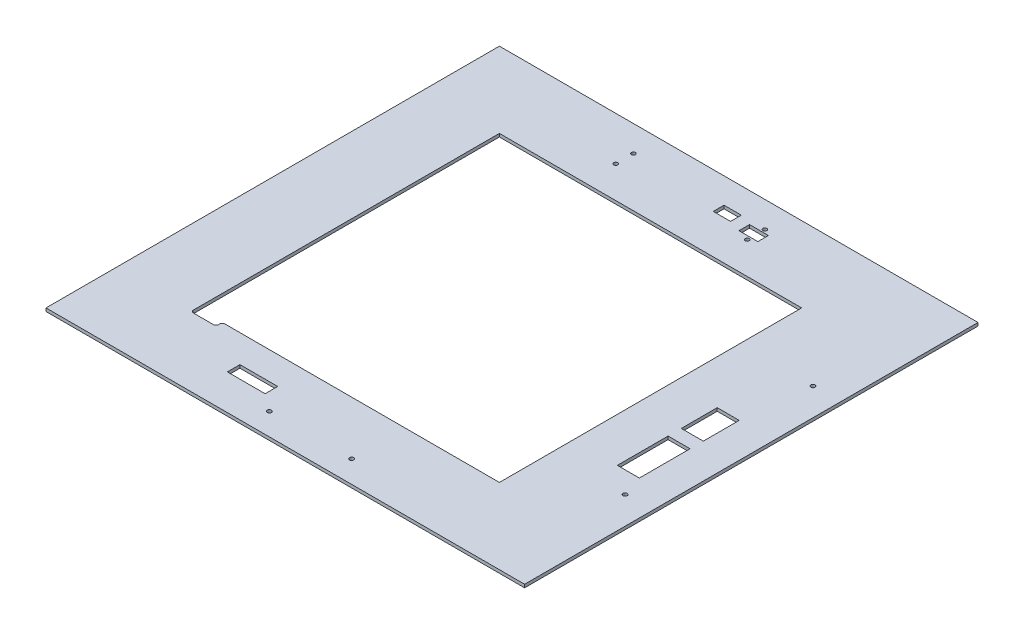
SolidWorks part; units mm, degrees
ref_plane "Front" through (0, 0, 0) normal (0, 0, 1) x (1, 0, 0)
ref_plane "Top" through (0, 0, 0) normal (0, 1, 0) x (1, 0, 0)
ref_plane "Right" through (0, 0, 0) normal (1, 0, 0) x (0, 0, -1)
sketch "Sketch1" plane through (0, 0, 0) normal (0, 1, 0) x (1, 0, 0)
  line L0 (-55, 0) -> (55, 0) construction
  line L1 (-242.5515, 228.6) -> (240.0485, 228.6)
  line L2 (-242.5515, 228.6) -> (-242.5515, -228.6)
  line L3 (-242.5515, -228.6) -> (240.0485, -228.6)
  line L4 (240.0485, 228.6) -> (240.0485, -228.6)
  line L5 (-242.5515, 228.6) -> (240.0485, -228.6) construction
  line L6 (-242.5515, -228.6) -> (240.0485, 228.6) construction
  line L7 (-166.3515, 152.4) -> (138.4485, 152.4)
  line L8 (-166.3515, 152.4) -> (-166.3515, -152.4)
  line L9 (-166.3515, -152.4) -> (138.4485, -152.4)
  line L10 (138.4485, 152.4) -> (138.4485, -152.4)
  line L11 (-166.3515, 152.4) -> (138.4485, -152.4) construction
  line L12 (-166.3515, -152.4) -> (138.4485, 152.4) construction
  line L13 (-160.0015, 146.05) -> (132.0985, 146.05)
  line L14 (-160.0015, 146.05) -> (-160.0015, -146.05)
  line L15 (-160.0015, -146.05) -> (132.0985, -146.05)
  line L16 (132.0985, 146.05) -> (132.0985, -146.05)
  line L17 (-160.0015, 146.05) -> (132.0985, -146.05) construction
  line L18 (-160.0015, -146.05) -> (132.0985, 146.05) construction
  line L19 (-166.3515, -152.4) -> (-140.9515, -152.4)
  line L20 (-166.3515, -152.4) -> (-166.3515, -158.75)
  line L21 (-166.3515, -158.75) -> (-140.9515, -158.75)
  line L22 (-140.9515, -152.4) -> (-140.9515, -158.75)
  line L24 (58.4385, 188.214) -> (39.3885, 188.214)
  line L25 (58.4385, 188.214) -> (58.4385, 198.882)
  line L26 (58.4385, 198.882) -> (39.3885, 198.882)
  line L27 (39.3885, 188.214) -> (39.3885, 198.882)
  line L28 (182.9854, -26.8512) -> (205.1825, -26.8512)
  line L29 (182.9854, -26.8512) -> (182.9854, -78.0068)
  line L30 (182.9854, -78.0068) -> (205.1825, -78.0068)
  line L31 (205.1825, -26.8512) -> (205.1825, -78.0068)
  line L32 (182.9854, -13.5376) -> (205.1825, -13.5376)
  line L33 (182.9854, -13.5376) -> (182.9854, 22.6879)
  line L34 (182.9854, 22.6879) -> (205.1825, 22.6879)
  line L35 (205.1825, -13.5376) -> (205.1825, 22.6879)
  line L40 (27.0379, 202.954) -> (9.5991, 202.954)
  line L41 (27.0379, 202.954) -> (27.0379, 192.0704)
  line L42 (27.0379, 192.0704) -> (9.5991, 192.0704)
  line L43 (9.5991, 202.954) -> (9.5991, 192.0704)
  line L44 (-95.2315, -180.3456) -> (-57.1315, -180.3456)
  line L45 (-95.2315, -180.3456) -> (-95.2315, -193.0456)
  line L46 (-95.2315, -193.0456) -> (-57.1315, -193.0456)
  line L47 (-57.1315, -180.3456) -> (-57.1315, -193.0456)
  circle A0 centre (51.3519, 202.311) radius 2
  circle A1 centre (51.3519, 184.531) radius 2
  circle A2 centre (-81.1091, 202.311) radius 2
  circle A3 centre (-81.1091, 184.531) radius 2
  circle A4 centre (212.3904, -99.5798) radius 2.0955
  circle A5 centre (212.3904, 89.828) radius 2.0955
  circle A6 centre (-39.6436, -206.2861) radius 2.1
  circle A7 centre (43.3382, -206.2861) radius 2.1
  point P0 (-1.2515, 0)
  point P6 (-44.5662, -1.1741)
  point P11 (-84.1987, 3.6789)
  point P21 (-13.9515, 0)
  point P22 (-13.9515, 0)
  point P23 (-1.2515, 0)
  dimension "D15" = 4
  dimension "D16" = 4
  dimension "D17" = 26.289
  dimension "D18" = 17.78
  dimension "D19" = 188.6966
  dimension "D20" = 132.461
  dimension "D22" = 27.6581
  dimension "D23" = 4.191
  dimension "D24" = 129.0202
  dimension "D26" = 4.2
  dimension "D27" = 22.3139
  dimension "D28" = 202.9079
  dimension "D29" = 82.9818
  dimension "D1" = 457.2
  dimension "D2" = 482.6
  dimension "D3" = 304.8
  dimension "D4" = 304.8
  dimension "D5" = 76.2
  dimension "D6" = 292.1
  dimension "D7" = 146.05
  dimension "D8" = 228.6
  dimension "D9" = 25.4
  dimension "D10" = 6.35
  dimension "D11" = 10.668
  dimension "D12" = 181.61
  dimension "D13" = 19.05
  dimension "D14" = 29.718
  dimension "D21" = 17.78
  dimension "D25" = 189.4078
  dimension "D30" = 12.7
  dimension "D31" = 185.42
  dimension "D32" = 38.1
extrude "Boss-Extrude1" add sketch "Sketch1" along normal blind 3.175 contours L4 L1 L2 L3 L7 L10 L9 L8 region at (-1.2515, 0, -221.9522)
fillet "Fillet1" radius 2.54 3 edges at (-140.9515, 1.5875, 158.75) (-166.3515, 1.5875, 158.75) (-140.9515, 1.5875, 152.4)
